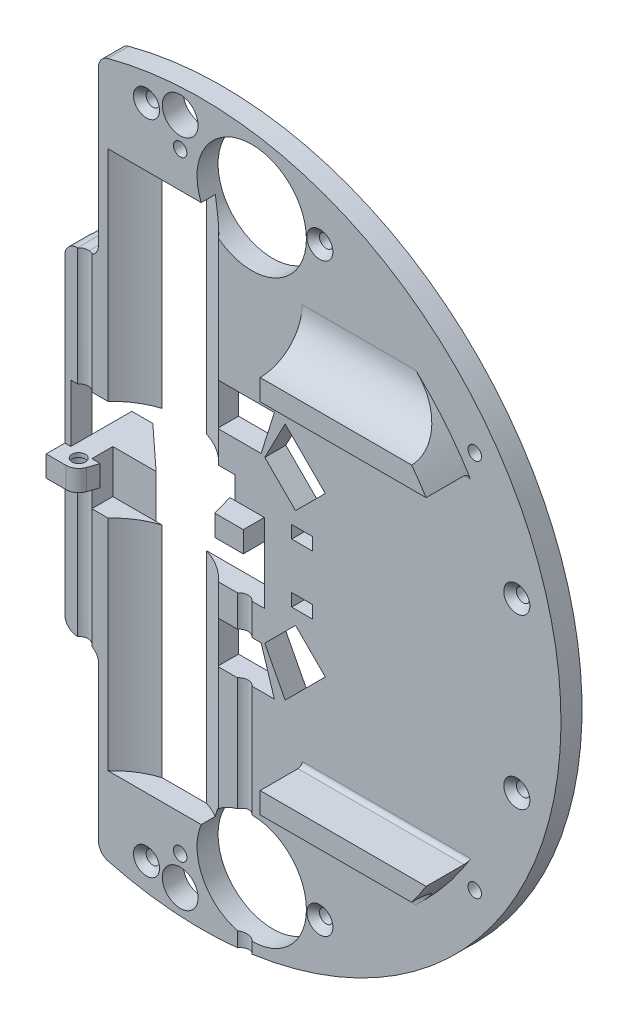
SolidWorks part; units mm, degrees
ref_plane "Front Plane" through (0, 0, 0) normal (1, 0, 0) x (0, 1, 0)
ref_plane "Top Plane" through (0, 0, 0) normal (0, 0, 1) x (0, 1, 0)
ref_plane "Right Plane" through (0, 0, 0) normal (0, 1, 0) x (-1, 0, 0)
sketch "Sketch1" plane through (0, 0, 0) normal (0, 0, 1) x (0, 1, 0)
  line L0 (0, 0) -> (0, -81.5088) construction
  line L1 (-40, 24.3888) -> (-40, 32.4114)
  line L2 (-40, 32.4114) -> (40, 32.4114)
  line L6 (-81.9478, 24.3888) -> (-40, 24.3888)
  line L7 (81.941, 24.4114) -> (40, 24.4114)
  line L8 (40, 24.4114) -> (40, 32.4114)
  arc A0 (-81.9478, 24.3888) -> (81.941, 24.4114) centre (0, 0) ccw
  circle A1 centre (-20, -75) radius 1.6
  circle A2 centre (20, -75) radius 1.6
  circle A3 centre (-69.5, -28.2) radius 1.6
  circle A9 centre (-78, 13) radius 1.6
  circle A10 centre (-79.5, 5) radius 4.25
  circle A11 centre (-69, -12) radius 13
  circle A16 centre (69, -12) radius 13
  circle A17 centre (79.5, 5) radius 4.25
  circle A18 centre (78, 13) radius 1.6
  circle A19 centre (69.5, -28.2) radius 1.6
  dimension "D1" = 171
  dimension "D3" = 3.2
  dimension "D7" = 3.2
  dimension "D8" = 78
  dimension "D13" = 5
  dimension "D14" = 69
  dimension "D16" = 40
  dimension "D2" = 75
  dimension "D4" = 20
  dimension "D5" = 69.5
  dimension "D6" = 28.2
  dimension "D9" = 40
  dimension "D10" = 13
  dimension "D11" = 8
  dimension "D12" = 79.5
  dimension "D15" = 12
extrude "Boss-Extrude2" add sketch "Sketch1" along normal blind 5
sketch "Sketch2" plane through (0, 0, 5) normal (0, 0, 1) x (1, 0, 0)
  line L1 (60, 45) -> (24, 45)
  line L3 (63.4429, 40) -> (24, 40)
  line L4 (24, 45) -> (24, 40)
  line L6 (24, -45) -> (24, -40)
  line L7 (63.4429, -40) -> (24, -40)
  line L8 (60, -45) -> (24, -45)
  arc A3 (60, -45) -> (63.4429, -40) centre (0, 0) ccw
  arc A4 (63.4429, 40) -> (60, 45) centre (0, 0) ccw
  dimension "D1" = 150
  dimension "D2" = 40
extrude "Boss-Extrude3" add sketch "Sketch2" along normal blind 10
fillet "Fillet1" radius 10 2 edges at (42, -45, 5) (42, 45, 5)
fillet "Fillet2" radius 1 2 edges at (43.7214, -40, 5) (43.7214, 40, 5)
sketch "Sketch5" plane through (0, 0, 5) normal (0, 0, 1) x (1, 0, 0)
  line L0 (0, 0) -> (93.3614, 0) construction
  circle A0 centre (65, 45) radius 1.6
  circle A2 centre (-5, 72.5) radius 1.6
  circle A4 centre (65, -45) radius 1.6
  circle A5 centre (-5, -72.5) radius 1.6
  dimension "D1" = 3.2
  dimension "D5" = 3.2
  dimension "D2" = 65
  dimension "D3" = 45
  dimension "D4" = 5
  dimension "D6" = 72.5
extrude "Cut-Extrude2" cut sketch "Sketch5" against normal blind 10
chamfer "Chamfer1" distance 1.5 angle 45 6 edges at (-14.6, -78, 5) (29.8, -69.5, 5) (76.6, -20, 5) (73.4, 20, 5) (26.6, 69.5, 5) (-11.4, 78, 5)
chamfer "Chamfer2" distance 1.5 angle 45 4 edges at (-3.4, 72.5, 0) (-3.4, -72.5, 0) (66.6, -45, 0) (66.6, 45, 0)
sketch "Sketch9" plane through (0, 0, 5) normal (0, 0, 1) x (1, 0, 0)
  line L1 (17.112, -24.1831) -> (24.1831, -17.112) construction
  line L6 (14.2376, -19.4864) -> (3.8798, -19.4864)
  line L8 (15.1085, -19.1155) -> (22.4153, -11.8087)
  line L10 (22.4153, -11.8087) -> (29.4864, -18.8798)
  line L11 (19.9404, -28.4257) -> (29.4864, -18.8798)
  line L12 (11.8087, -22.4153) -> (29.4864, -18.8798) construction
  line L13 (22.4153, -11.8087) -> (18.8798, -29.4864) construction
  line L14 (0, 0) -> (90.6538, 0) construction
  line L23 (17.3798, -29.4864) -> (3.8798, -29.4864)
  line L24 (3.8798, -19.4864) -> (3.8798, -29.4864)
  line L25 (18.8798, -19.4864) -> (3.8798, -29.4864) construction
  line L26 (18.8798, -29.4864) -> (3.8798, -19.4864) construction
  line L32 (15.1085, -19.1155) -> (19.9404, -28.4257)
  line L33 (17.3798, -29.4864) -> (14.2376, -19.4864)
  line L34 (17.3798, 29.4864) -> (14.2376, 19.4864)
  line L35 (14.2376, 19.4864) -> (3.8798, 19.4864)
  line L36 (3.8798, 19.4864) -> (3.8798, 29.4864)
  line L37 (17.3798, 29.4864) -> (3.8798, 29.4864)
  line L38 (15.1085, 19.1155) -> (19.9404, 28.4257)
  line L39 (15.1085, 19.1155) -> (22.4153, 11.8087)
  line L40 (22.4153, 11.8087) -> (29.4864, 18.8798)
  line L41 (19.9404, 28.4257) -> (29.4864, 18.8798)
  point P1 (11.3798, -24.4864)
  point P6 (20.6475, -20.6475)
  dimension "D1" = 10
  dimension "D2" = 15
  dimension "D3" = 15
  dimension "D4" = 10
  dimension "D6" = 1.5
  dimension "D7" = 1.5
extrude "Cut-Extrude3" cut sketch "Sketch9" against normal blind 10
sketch "Sketch10" plane through (0, 0, 0) normal (0, 1, 0) x (-1, 0, 0)
  line L0 (-85.5, 0) -> (24.4114, 0) construction
  circle A0 centre (9, 17) radius 17.8
  dimension "D1" = 35.6
  dimension "D2" = 17
  dimension "D3" = 9
extrude "Cut-Extrude4" cut sketch "Sketch10" against normal blind 64 and the other way blind 64
sketch "Sketch11" plane through (0, 0, 5) normal (0, 0, 1) x (1, 0, 0)
  line L0 (-26, -1.7) -> (-31, -1.7)
  line L1 (8, 12) -> (-25, 12)
  line L3 (15, -12) -> (-26, -12)
  line L4 (-26, -1.7) -> (-26, -12)
  line L5 (15, -12) -> (15, 1.7)
  line L6 (8, 12) -> (8, 1.7)
  line L7 (8, 1.7) -> (15, 1.7)
  line L8 (-31, -1.7) -> (-31, 12)
  line L9 (-31, 12) -> (-25, 12)
  point P0 (0, 0)
  dimension "D1" = 24
  dimension "D2" = 12
  dimension "D3" = 6
  dimension "D4" = 15
  dimension "D5" = 7
  dimension "D6" = 1.7
  dimension "D7" = 1.7
  dimension "D8" = 5
extrude "Cut-Extrude5" cut sketch "Sketch11" against normal blind 62.5
sketch "Sketch12" plane through (0, 0, 5) normal (0, 0, 1) x (1, 0, 0)
  line L1 (10.2402, 0) -> (10.2402, 1.7) construction
  line L2 (-6.5732, 0.8) -> (-6.5732, 1.7) construction
  line L3 (-6.5732, 1.7) -> (10.2402, 1.7) construction
  line L4 (-16.3028, 0) -> (-16.3028, -1.7) construction
  line L5 (-8.6264, 0) -> (-8.6264, -0.9) construction
  dimension "D1" = 1.7
  dimension "D2" = 1.7
ref_plane "Plane2" through (0, 1.7, 0) normal (0, -1, 0) x (1, 0, 0)
sketch "Sketch13" plane through (0, 0, 5) normal (0, 0, 1) x (1, 0, 0)
  line L1 (15, 1.7) -> (6.7929, 1.7)
  line L2 (15, 1.7) -> (15, 6.7)
  line L3 (15, 6.7) -> (6.7929, 6.7)
  line L4 (6.7929, 1.7) -> (6.7929, 6.7)
  dimension "D1" = 5
extrude "Boss-Extrude4" add sketch "Sketch13" along normal blind 5
sketch "Sketch14" plane through (0, 1.7, 0) normal (0, -1, 0) x (1, 0, 0)
  circle A1 centre (10.3299, 6.4392) radius 2.25
  dimension "D2" = 4.5
extrude "Cut-Extrude6" cut sketch "Sketch14" against normal blind 4 and the other way blind 110
sketch "Sketch15" plane through (0, 1.7, 0) normal (0, -1, 0) x (1, 0, 0)
  line L2 (6.7929, 5) -> (6.7929, 10)
  line L3 (6.7929, 10) -> (8.2341, 10)
  line L4 (6.7929, 5) -> (8.2341, 10)
extrude "Cut-Extrude7" cut sketch "Sketch15" against normal blind 15
sketch "Sketch16" plane through (0, 0, 5) normal (0, 0, 1) x (1, 0, 0)
  line L0 (-32.4114, 40) -> (-32.4114, -40) construction
  line L1 (-32.4114, -1.7) -> (-24, -1.7)
  line L2 (-32.4114, -1.7) -> (-32.4114, -6.7)
  line L3 (-32.4114, -6.7) -> (-24, -6.7)
  line L4 (-24, -1.7) -> (-24, -6.7)
  dimension "D1" = 5
  dimension "D2" = 1.7
extrude "Boss-Extrude5" add sketch "Sketch16" along normal blind 5
sketch "Sketch17" plane through (0, -6.7, 0) normal (0, -1, 0) x (1, 0, 0)
  circle A0 centre (-27.6683, 6.4392) radius 2.25
  dimension "D1" = 4.5
extrude "Cut-Extrude8" cut sketch "Sketch17" against normal blind 4 and the other way blind 40
sketch "Sketch18" plane through (0, -6.7, 0) normal (0, -1, 0) x (1, 0, 0)
  line L0 (-24, 5) -> (-24.8314, 7.4156)
  line L1 (-32.4114, 10) -> (-24, 10) construction
  line L2 (-25.7209, 10) -> (-24, 10)
  line L3 (-24, 10) -> (-24, 5)
  line L5 (-27.6683, 9.4394) -> (-32.4114, 9.4394)
  line L6 (-32.4114, 10) -> (-32.4114, 5) construction
  line L7 (-32.4114, 9.4394) -> (-32.4114, 10)
  line L8 (-32.4114, 10) -> (-25.7209, 10)
  arc A1 (-24.8314, 7.4156) -> (-27.6683, 9.4394) centre (-27.6683, 6.4392) ccw
extrude "Cut-Extrude9" cut sketch "Sketch18" against normal blind 7
sketch "Sketch19" plane through (0, -2.7, 0) normal (0, -1, 0) x (1, 0, 0)
  circle A0 centre (-27.6683, 6.4392) radius 1.6
  dimension "D1" = 3.2
extrude "Cut-Extrude10" cut sketch "Sketch19" against normal blind 7
sketch "Sketch20" plane through (0, -1.7, 0) normal (0, 1, 0) x (-1, 0, 0)
  circle A0 centre (27.6683, 6.4392) radius 2.25
  dimension "D1" = 4.5
extrude "Cut-Extrude11" cut sketch "Sketch20" along normal blind 45
sketch "Sketch21" plane through (0, 0, 0) normal (0, 0, -1) x (1, 0, 0)
  line L1 (69.738, 4) -> (6.369, 4)
  line L2 (69.738, 4) -> (69.738, -4)
  line L3 (69.738, -4) -> (6.369, -4)
  line L4 (6.369, 4) -> (6.369, -4)
  dimension "D1" = 8
  dimension "D2" = 4
extrude "Cut-Extrude12" cut sketch "Sketch21" against normal blind 3
sketch "Sketch22" plane through (0, 0, 0) normal (0, 0, -1) x (1, 0, 0)
  line L0 (0, 0) -> (46.1564, 0) construction
  line L1 (21.5, -5.5) -> (26.5, -5.5)
  line L2 (21.5, -5.5) -> (21.5, -8.5)
  line L3 (21.5, -8.5) -> (26.5, -8.5)
  line L4 (26.5, -5.5) -> (26.5, -8.5)
  line L5 (21.5, -5.5) -> (26.5, -8.5) construction
  line L6 (21.5, -8.5) -> (26.5, -5.5) construction
  line L11 (21.5, 8.5) -> (26.5, 5.5) construction
  line L12 (21.5, 5.5) -> (26.5, 8.5) construction
  line L13 (26.5, 5.5) -> (26.5, 8.5)
  line L14 (21.5, 8.5) -> (26.5, 8.5)
  line L15 (21.5, 5.5) -> (21.5, 8.5)
  line L16 (21.5, 5.5) -> (26.5, 5.5)
  point P0 (24, -7)
  point P12 (24, 7)
  dimension "D1" = 5
  dimension "D2" = 3
  dimension "D3" = 7
  dimension "D4" = 24
extrude "Cut-Extrude13" cut sketch "Sketch22" against normal blind 5
sketch "Sketch23" plane through (0, 0, 5) normal (0, 0, 1) x (1, 0, 0)
fillet "Fillet3" radius 3 6 edges at (-24.3888, -40, 2.5) (-32.4114, -40, 2.5) (-24.4114, 40, 2.5) (-32.4114, 40, 2.5) (-24.4114, 81.941, 2.5) (-24.3888, -81.9478, 2.5)
sketch "Sketch24" plane through (0, 0, 0) normal (0, 0, -1) x (1, 0, 0)
  line L0 (-31, 1.7) -> (-31, 39.5449)
  line L1 (-26, 1.7) -> (-26, 40.3453)
  line L2 (-29.4114, 40) -> (-27.3888, 40.004)
  line L3 (-31, 1.7) -> (-26, 1.7)
  line L4 (69.738, 0) -> (25.2723, 0) construction
  line L5 (69.738, -4) -> (69.738, 4) construction
  line L7 (-29.4114, -40) -> (-27.3888, -40.004)
  line L8 (-26, -12) -> (-26, -40.3453)
  line L9 (-31, -12) -> (-31, -39.5449)
  line L10 (-31, -12) -> (-26, -12)
  line L11 (-14.2764, -12) -> (-31, -12) construction
  arc A0 (-29.4114, 40) -> (-32.4114, 37) centre (-29.4114, 37) ccw construction
  arc A1 (-29.4114, 40) -> (-31, 39.5449) centre (-29.4114, 37) ccw
  arc A2 (-27.3888, 40.004) -> (-26, 40.3453) centre (-27.3888, 43) ccw
  arc A3 (-27.3888, -40.004) -> (-26, -40.3453) centre (-27.3888, -43) cw
  arc A4 (-29.4114, -40) -> (-31, -39.5449) centre (-29.4114, -37) cw
extrude "Boss-Extrude6" add sketch "Sketch24" along normal blind 9.5
sketch "Sketch25" plane through (-31, 0, 0) normal (-1, 0, 0) x (0, -1, 0)
  line L0 (-37, 0) -> (37, 0) construction
  circle A0 centre (13, -5.25) radius 2.25
  circle A1 centre (-13, -5.25) radius 2.25
  dimension "D1" = 4.5
  dimension "D2" = 4.5
  dimension "D3" = 26
  dimension "D4" = 13
  dimension "D5" = 5.25
extrude "Cut-Extrude14" cut sketch "Sketch25" against normal blind 9.5
sketch "Sketch27" plane through (0, 12, 0) normal (0, -1, 0) x (1, 0, 0)
  line L0 (-26, -9.5) -> (-15.7165, 0)
  line L1 (-22.19, 0) -> (85.5, 0) construction
  line L2 (-26, -9.5) -> (-26, 0)
  line L3 (-26, 0) -> (-15.7165, 0)
  dimension "D1" = 14
extrude "Boss-Extrude7" add sketch "Sketch27" against normal blind 30.35
sketch "Sketch28" plane through (0, -1.7, 0) normal (0, 1, 0) x (-1, 0, 0)
  line L0 (26, -9.5) -> (15.7165, 0)
  line L1 (15.7165, 0) -> (26, 0)
  line L2 (26, 0) -> (26, -9.5)
extrude "Boss-Extrude8" add sketch "Sketch28" against normal blind 39.45
